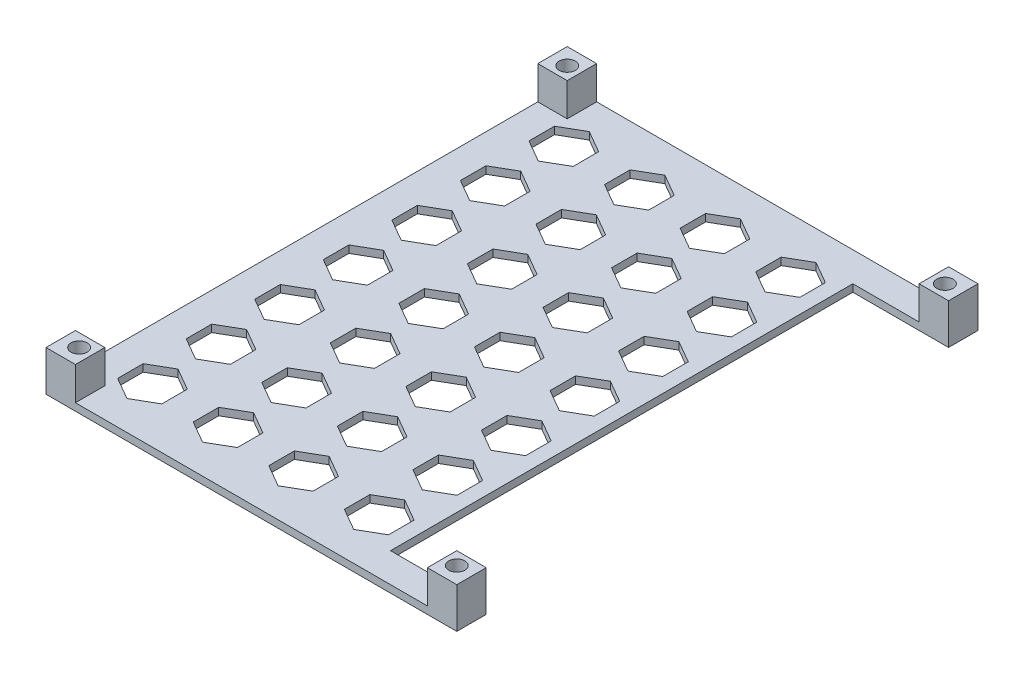
SolidWorks part; units mm, degrees
ref_plane "Front Plane" through (0, 0, 0) normal (0, 0, 1) x (1, 0, 0)
ref_plane "Top Plane" through (0, 0, 0) normal (0, 1, 0) x (1, 0, 0)
ref_plane "Right Plane" through (0, 0, 0) normal (1, 0, 0) x (0, 0, -1)
sketch "Sketch1" plane through (0, 0, 0) normal (0, 1, 0) x (1, 0, 0)
  line L0 (0, 0) -> (55.8, 0)
  line L5 (55.8, 0) -> (55.8, 4)
  line L6 (55.8, 4) -> (42.8, 4)
  line L7 (42.8, 4) -> (42.8, 66.8)
  line L8 (42.8, 66.8) -> (55.8, 66.8)
  line L9 (55.8, 66.8) -> (55.8, 70.8)
  line L10 (55.8, 70.8) -> (0, 70.8)
  line L11 (0, 70.8) -> (0, 0)
  dimension "D1" = 55.8
  dimension "D2" = 13
  dimension "D3" = 70.8
  dimension "D4" = 4
  dimension "D5" = 4
extrude "Boss-Extrude1" add sketch "Sketch1" along normal blind 1
sketch "Sketch2" plane through (0, 1, 0) normal (0, 1, 0) x (1, 0, 0)
  line L0 (42.8, 66.8) -> (0, 66.8) construction
  line L1 (0, 70.8) -> (0, 0) construction
  line L2 (4, 70.8) -> (4, 0) construction
  line L3 (55.8, 70.8) -> (0, 70.8) construction
  line L5 (0, 0) -> (55.8, 0) construction
  line L6 (40.8, 66.8) -> (40.8, 0) construction
  line L7 (42.8, 4) -> (42.8, 66.8) construction
  line L9 (7, 66.8) -> (4, 65.0679)
  line L10 (4, 65.0679) -> (4, 61.6038)
  line L11 (4, 61.6038) -> (7, 59.8718)
  line L12 (7, 59.8718) -> (10, 61.6038)
  line L13 (10, 61.6038) -> (10, 65.0679)
  line L14 (10, 65.0679) -> (7, 66.8)
  circle A0 centre (7, 63.3359) radius 3 construction
  dimension "D1" = 4
  dimension "D2" = 2
  dimension "D3" = 6
extrude "Cut-Extrude1" cut sketch "Sketch2" against normal up to surface (1 mm away) up to face at (38.6, 0, -35.4)
pattern_linear "LPattern1" count 4 spacing 10.2667 along (1, 0, 0) count 7 spacing 9.312 along (0, 0, 1) of "Cut-Extrude1"
sketch "Sketch3" plane through (0, 1, 0) normal (0, 1, 0) x (1, 0, 0)
  line L0 (42.8, 66.8) -> (55.8, 66.8) construction
  line L1 (0, 70.8) -> (4, 70.8)
  line L2 (0, 70.8) -> (0, 66.8)
  line L3 (0, 66.8) -> (4, 66.8)
  line L4 (4, 70.8) -> (4, 66.8)
  line L5 (55.8, 70.8) -> (51.8, 70.8)
  line L6 (55.8, 70.8) -> (55.8, 66.8)
  line L7 (55.8, 66.8) -> (51.8, 66.8)
  line L8 (51.8, 70.8) -> (51.8, 66.8)
  line L9 (0, 0) -> (55.8, 0) construction
  line L10 (55.8, 4) -> (51.8, 4)
  line L11 (55.8, 4) -> (55.8, 0)
  line L12 (55.8, 0) -> (51.8, 0)
  line L13 (51.8, 4) -> (51.8, 0)
  line L15 (0, 0) -> (4, 0)
  line L16 (0, 0) -> (0, 4)
  line L17 (0, 4) -> (4, 4)
  line L18 (4, 0) -> (4, 4)
  dimension "D1" = 4
extrude "Boss-Extrude2" add sketch "Sketch3" along normal blind 4.5
sketch "Sketch4" plane through (0, 5.5, 0) normal (0, 1, 0) x (1, 0, 0)
  line L3 (0, 68.55) -> (55.8, 68.55) construction
  line L4 (0, 70.8) -> (0, 66.8) construction
  line L5 (55.8, 66.8) -> (55.8, 70.8) construction
  line L6 (4, 70.8) -> (0, 70.8) construction
  circle A0 centre (2.25, 68.55) radius 1.1
  circle A1 centre (53.55, 68.55) radius 1.1
  dimension "D3" = 2.2
  dimension "D1" = 2.25
  dimension "D2" = 2.25
  dimension "D4" = 2.25
extrude "Cut-Extrude2" cut sketch "Sketch4" against normal up to surface (5.5 mm away) up to face at (17.2667, 0, -63.3359)
ref_plane "Plane1" through (0, 0, -35.4) normal (0, 0, -1) x (-1, 0, 0)
mirror "Mirror1" about plane through (0, 0, -35.4) normal (0, 0, -1) of "Cut-Extrude2"
